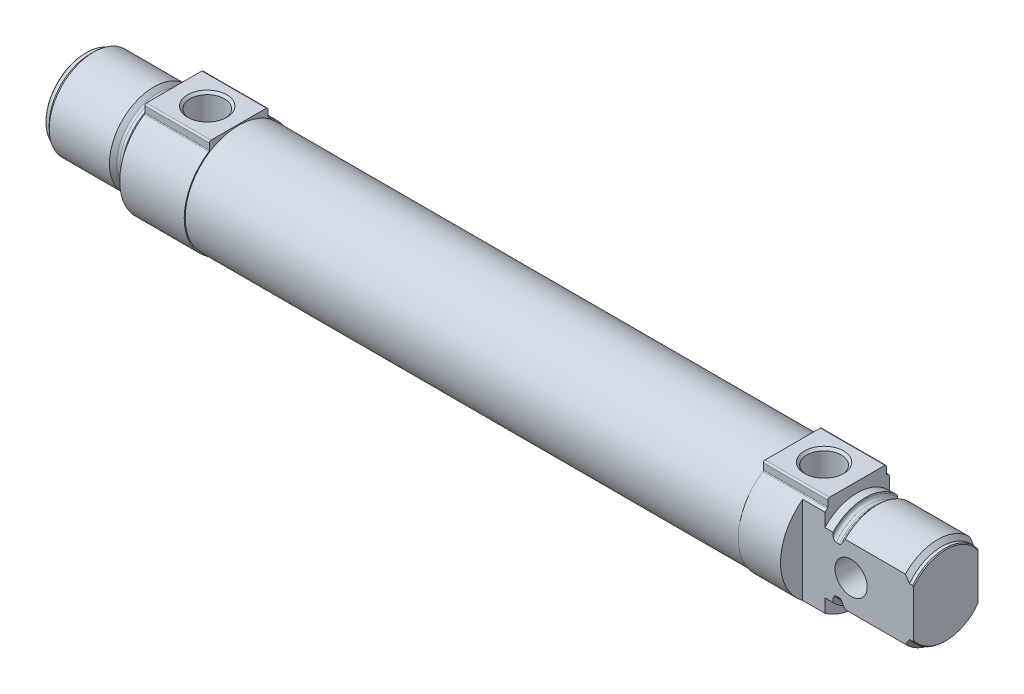
SolidWorks part; units mm, degrees
ref_plane "Ebene vorne" through (0, 0, 0) normal (0, 0, 1) x (1, 0, 0)
ref_plane "Ebene oben" through (0, 0, 0) normal (0, 1, 0) x (1, 0, 0)
ref_plane "Ebene rechts" through (0, 0, 0) normal (1, 0, 0) x (0, 0, -1)
sketch "Skizze1" plane through (0, 0, 0) normal (0, 0, 1) x (1, 0, 0)
  line L0 (0, 0) -> (0, 9.8)
  line L1 (0, 9.8) -> (0.2, 10)
  line L2 (0.2, 10) -> (1, 10)
  line L3 (1, 10) -> (2, 11)
  line L4 (2, 11) -> (16.95, 11)
  line L5 (16.95, 11) -> (17.8657, 10.0843)
  line L6 (18.4314, 9.85) -> (19.2, 9.85)
  line L7 (20, 10.65) -> (20, 11)
  line L8 (20, 11) -> (22, 11)
  line L9 (22, 11) -> (22, 0)
  line L10 (22, 0) -> (0, 0)
  line L11 (22, 0) -> (0, 0) construction
  arc A0 (17.8657, 10.0843) -> (18.4314, 9.85) centre (18.4314, 10.65) ccw
  arc A1 (19.2, 9.85) -> (20, 10.65) centre (19.2, 10.65) ccw
revolve "Rotation1" add sketch "Skizze1" angle 360 about L11 reverse direction yes
cosmetic thread "Gewindedarstellung1" parameters "D1"=15.87, "D2"=20.16
ref_plane "Ebene1" through (31.8, 0, 0) normal (1, 0, 0) x (0, 0, -1)
ref_plane "Ebene2" through (10.5, 0, 0) normal (1, 0, 0) x (0, 0, -1)
ref_plane "Ebene3" through (0, -16, 0) normal (0, 1, 0) x (1, 0, 0)
ref_plane "Ebene4" through (0, 14.9, 0) normal (0, 1, 0) x (1, 0, 0)
ref_plane "Ebene5" through (0, 0, 0) normal (0, 1, 0) x (1, 0, 0)
ref_plane "Ebene6" through (0, 0, 0) normal (0, 1, 0) x (1, 0, 0)
ref_plane "Ebene7" through (22, 0, 0) normal (1, 0, 0) x (0, 0, -1)
ref_plane "Ebene8" through (22, 0, 0) normal (1, 0, 0) x (0, 0, -1)
ref_plane "Ebene9" through (35, 0, 0) normal (1, 0, 0) x (0, 0, -1)
ref_plane "Ebene10" through (26.5, 0, 0) normal (1, 0, 0) x (0, 0, -1)
ref_plane "Ebene11" through (46.5, 0, 0) normal (1, 0, 0) x (0, 0, -1)
sketch "Skizze2" plane through (22, 0, 0) normal (1, 0, 0) x (0, 0, -1)
  line L0 (7.25, 11.5515) -> (7.25, 13.1)
  line L1 (6.85, 13.5) -> (-6.85, 13.5)
  line L2 (-7.25, 13.1) -> (-7.25, 11.5515)
  arc A0 (-7.3859, 11.3004) -> (7.3859, 11.3004) centre (0, 0) ccw
  arc A1 (7.3859, 11.3004) -> (7.25, 11.5515) centre (7.55, 11.5515) cw
  arc A2 (7.25, 13.1) -> (6.85, 13.5) centre (6.85, 13.1) ccw
  arc A3 (-6.85, 13.5) -> (-7.25, 13.1) centre (-6.85, 13.1) ccw
  arc A4 (-7.25, 11.5515) -> (-7.3859, 11.3004) centre (-7.55, 11.5515) cw
extrude "Aufsatz-Linear austragen1" add sketch "Skizze2" along normal blind 16
ref_plane "Ebene12" through (34, 0, 0) normal (1, 0, 0) x (0, 0, -1)
ref_plane "Ebene13" through (0, 0, 0) normal (0, 0, 1) x (1, 0, 0)
ref_plane "Ebene14" through (0, 0, -9.1) normal (0, 0, 1) x (1, 0, 0)
ref_plane "Ebene15" through (0, 0, 0) normal (0, 1, 0) x (1, 0, 0)
ref_plane "Ebene16" through (0, 6.9, 0) normal (0, 1, 0) x (1, 0, 0)
ref_plane "Ebene17" through (0, 0, -6.6) normal (0, 0, 1) x (1, 0, 0)
ref_plane "Ebene18" through (0, 0, 0) normal (0, 1, 0) x (1, 0, 0)
ref_plane "Ebene19" through (0, 6.9, 0) normal (0, 1, 0) x (1, 0, 0)
ref_plane "Ebene20" through (0, 7.8206, -1.379) normal (0, 0.9848, -0.1736) x (1, 0, 0)
ref_plane "Ebene21" through (0, 6.3434, -1.1185) normal (0, 0.9848, -0.1736) x (1, 0, 0)
sketch "Skizze3" plane through (0, 0, 0) normal (0, 0, 1) x (1, 0, 0)
  line L0 (38, 0) -> (38, 13.25)
  line L1 (38, 13.25) -> (175.5, 13.25)
  line L2 (175.5, 13.25) -> (175.5, 0)
  line L3 (175.5, 0) -> (38, 0)
  line L4 (175.5, 0) -> (38, 0) construction
revolve "Rotation2" add sketch "Skizze3" angle 360 about L4 reverse direction yes
ref_plane "Ebene22" through (175.5, 0, 0) normal (1, 0, 0) x (0, 0, -1)
sketch "Skizze4" plane through (175.5, 0, 0) normal (1, 0, 0) x (0, 0, -1)
  line L0 (7.25, 11.5515) -> (7.25, 13.1)
  line L1 (6.85, 13.5) -> (-6.85, 13.5)
  line L2 (-7.25, 13.1) -> (-7.25, 11.5515)
  arc A0 (-7.3859, 11.3004) -> (7.3859, 11.3004) centre (0, 0) ccw
  arc A1 (7.3859, 11.3004) -> (7.25, 11.5515) centre (7.55, 11.5515) cw
  arc A2 (7.25, 13.1) -> (6.85, 13.5) centre (6.85, 13.1) ccw
  arc A3 (-6.85, 13.5) -> (-7.25, 13.1) centre (-6.85, 13.1) ccw
  arc A4 (-7.25, 11.5515) -> (-7.3859, 11.3004) centre (-7.55, 11.5515) cw
extrude "Aufsatz-Linear austragen2" add sketch "Skizze4" along normal blind 16
ref_plane "Ebene23" through (179.3, 0, 0) normal (1, 0, 0) x (0, 0, -1)
ref_plane "Ebene24" through (179.5, 0, 0) normal (1, 0, 0) x (0, 0, -1)
ref_plane "Ebene25" through (0, 0, 6.6) normal (0, 0, 1) x (1, 0, 0)
ref_plane "Ebene26" through (0, 0, 0) normal (0, 1, 0) x (1, 0, 0)
ref_plane "Ebene27" through (0, 6.9, 0) normal (0, 1, 0) x (1, 0, 0)
ref_plane "Ebene28" through (0, 7.8206, 1.379) normal (0, 0.9848, 0.1736) x (1, 0, 0)
ref_plane "Ebene29" through (0, 6.3434, 1.1185) normal (0, 0.9848, 0.1736) x (1, 0, 0)
ref_plane "Ebene30" through (239.5, 0, 0) normal (1, 0, 0) x (0, 0, -1)
sketch "Skizze5" plane through (0, 0, 0) normal (0, 0, 1) x (1, 0, 0)
  line L0 (191.5, 0) -> (191.5, 11)
  line L1 (191.5, 11) -> (193.5, 11)
  line L2 (193.5, 11) -> (193.5, 10.65)
  line L3 (194.3, 9.85) -> (195.0686, 9.85)
  line L4 (195.6343, 10.0843) -> (196.55, 11)
  line L5 (196.55, 11) -> (211.5, 11)
  line L6 (211.5, 11) -> (212.5, 10)
  line L7 (212.5, 10) -> (213.3, 10)
  line L8 (213.3, 10) -> (213.5, 9.8)
  line L9 (213.5, 9.8) -> (213.5, 0)
  line L10 (213.5, 0) -> (191.5, 0)
  line L11 (213.5, 0) -> (191.5, 0) construction
  arc A0 (193.5, 10.65) -> (194.3, 9.85) centre (194.3, 10.65) ccw
  arc A1 (195.0686, 9.85) -> (195.6343, 10.0843) centre (195.0686, 10.65) ccw
revolve "Rotation3" add sketch "Skizze5" angle 360 about L11 reverse direction yes
cosmetic thread "Gewindedarstellung2" parameters "D1"=14.87, "D2"=20.16
ref_plane "Ebene31" through (226.5, 0, 0) normal (1, 0, 0) x (0, 0, -1)
ref_plane "Ebene32" through (235, 0, 0) normal (1, 0, 0) x (0, 0, -1)
ref_plane "Ebene33" through (215, 0, 0) normal (1, 0, 0) x (0, 0, -1)
sketch "Skizze6" plane through (0, 0, 0) normal (0, 1, 0) x (1, 0, 0)
  line L0 (186, 24) -> (186, 8)
  line L1 (186, 8) -> (213.5, 8)
  line L2 (213.5, 8) -> (213.5, -8)
  line L3 (213.5, -8) -> (186, -8)
  line L4 (186, -8) -> (186, -24)
  line L5 (186, -24) -> (229.5, -24)
  line L6 (229.5, -24) -> (229.5, 24)
  line L7 (229.5, 24) -> (186, 24)
extrude "Schnitt-Linear austragen1" cut sketch "Skizze6" along normal blind 13.5 and the other way blind 13.5
ref_plane "Ebene34" through (198, 0, 0) normal (1, 0, 0) x (0, 0, -1)
hole_wizard "Bohrung1" positions "Skizze8" profile "Skizze7" legacy
sketch "Skizze8" plane through (0, 0, -8) normal (0, 0, -1) x (-1, 0, 0)
  point P0 (-198, 0)
sketch "Skizze7" plane through (198, 0, -8) normal (1, 0, 0) x (0, 1, 0)
  line L0 (0, 0) -> (0, 16)
  line L1 (0, 16) -> (4, 16)
  line L2 (4, 16) -> (4, 0)
  line L3 (4, 0) -> (0, 0)
  line L4 (0, 110) -> (0, -10) construction
  dimension "Durchmesser" = 8
  dimension "Tiefe" = 16
hole_wizard "Bohrung2" positions "Skizze10" profile "Skizze9" legacy
sketch "Skizze10" plane through (0, 13.5, 0) normal (0, 1, 0) x (1, 0, 0)
  point P0 (30.2, 0)
sketch "Skizze9" plane through (30.2, 13.5, 0) normal (1, 0, 0) x (0, 0, 1)
  line L0 (0, 0) -> (0, 13.5)
  line L1 (0, 13.5) -> (4.283, 13.5)
  line L2 (4.283, 13.5) -> (4.283, 0.581)
  line L3 (4.283, 0.581) -> (4.864, 0)
  line L4 (4.864, 0) -> (0, 0)
  line L5 (0, -6.4453) -> (0, 115.525) construction
  line L6 (-4.283, 0.581) -> (-4.864, 0) construction
  dimension "Durchmesser" = 8.566
  dimension "Tiefe" = 13.5
  dimension "Senkwinkel1" = 90
  dimension "Senkdurchmesser3" = 9.728
cosmetic thread "Gewindedarstellung3" parameters "D1"=8.5, "D2"=9.728
hole_wizard "Bohrung3" positions "Skizze12" profile "Skizze11" legacy
sketch "Skizze12" plane through (0, 13.5, 0) normal (0, 1, 0) x (1, 0, 0)
  point P0 (183.3, 0)
sketch "Skizze11" plane through (183.3, 13.5, 0) normal (1, 0, 0) x (0, 0, 1)
  line L0 (0, 0) -> (0, 18.4728)
  line L1 (0, 18.4728) -> (4.283, 16)
  line L2 (4.283, 16) -> (4.283, 0.581)
  line L3 (4.283, 0.581) -> (4.864, 0)
  line L4 (4.864, 0) -> (0, 0)
  line L5 (0, -14.3089) -> (0, 102.4216) construction
  line L6 (0, 18.4728) -> (-4.283, 16) construction
  line L7 (-4.283, 0.581) -> (-4.864, 0) construction
  dimension "Durchmesser" = 8.566
  dimension "Tiefe" = 16
  dimension "Senkdurchmesser1" = 9.728
  dimension "Senkwinkel1" = 90
  dimension "Spitzenwinkel" = 120
cosmetic thread "Gewindedarstellung4" parameters "D1"=8, "D2"=9.728
sketch "Skizze13" plane through (0, 0, 0) normal (0, 0, 1) x (1, 0, 0)
  line L0 (-6, 0) -> (-6, 5)
  line L1 (-6, 5) -> (52.6, 5)
  line L2 (52.6, 5) -> (52.6, 12.5)
  line L3 (52.6, 12.5) -> (158.85, 12.5)
  line L4 (158.85, 12.5) -> (158.85, 0)
  line L5 (158.85, 0) -> (-6, 0)
  line L6 (158.85, 0) -> (-6, 0) construction
revolve "Schnitt-Rotation1" cut sketch "Skizze13" angle 360 about L6 reverse direction yes
ref_plane "Ebene35" through (-6, 0, 0) normal (1, 0, 0) x (0, 0, -1)
ref_plane "Ebene36" through (0, 13.5, 0) normal (0, 1, 0) x (1, 0, 0)
ref_plane "Ebene37" through (8.5, 0, 0) normal (1, 0, 0) x (0, 0, -1)
ref_plane "Ebene38" through (0, 0, 0) normal (1, 0, 0) x (0, 0, -1)
ref_plane "Ebene39" through (22, 0, 0) normal (1, 0, 0) x (0, 0, -1)
ref_plane "Ebene40" through (191.5, 0, 0) normal (1, 0, 0) x (0, 0, -1)
ref_plane "Ebene41" through (22, 0, 0) normal (1, 0, 0) x (0, 0, -1)
ref_plane "Ebene42" through (0, 13.5, 0) normal (0, 1, 0) x (1, 0, 0)
ref_plane "Ebene43" through (47.5, 0, 0) normal (1, 0, 0) x (0, 0, -1)
ref_plane "Ebene44" through (166, 0, 0) normal (1, 0, 0) x (0, 0, -1)
ref_plane "Ebene45" through (0, 0, 0) normal (0, 0, 1) x (1, 0, 0)
ref_plane "Ebene46" through (22, 0, 0) normal (1, 0, 0) x (0, 0, -1)
ref_plane "Ebene47" through (0, 13.5, 0) normal (0, 1, 0) x (1, 0, 0)
ref_plane "FDT_FRONT XY" through (22, 0, 0) normal (1, 0, 0) x (0, 0, -1)
ref_plane "FDT_FRONT XZ" through (0, 0, 0) normal (0, -1, 0) x (-1, 0, 0)
ref_plane "FDT_FRONT YZ" through (0, 0, 0) normal (0, 0, -1) x (-1, 0, 0)
ref_axis "FDT_FRONT X" through (22, 0, 80.9) along (0, 0, -1)
ref_axis "FDT_FRONT Y" through (22, -50, 0) along (0, 1, 0)
ref_axis "FDT_FRONT Z" through (80.9, 0, 0) along (-1, 0, 0)
sketch3d "FDT_FRONT"
  point P0 (22, 0, 0)
ref_plane "FDT_QSFRONT XY" through (0, 13.5, 0) normal (0, 1, 0) x (1, 0, 0)
ref_plane "FDT_QSFRONT XZ" through (30.2, 0, 0) normal (-1, 0, 0) x (0, 0, 1)
ref_plane "FDT_QSFRONT YZ" through (0, 0, 0) normal (0, 0, 1) x (1, 0, 0)
ref_axis "FDT_QSFRONT X" through (30.2, 13.5, -50) along (0, 0, 1)
ref_axis "FDT_QSFRONT Y" through (-80.9, 13.5, 0) along (1, 0, 0)
ref_axis "FDT_QSFRONT Z" through (30.2, 50, 0) along (0, -1, 0)
sketch3d "FDT_QSFRONT"
  point P0 (30.2, 13.5, 0)
ref_plane "FDT_QSREAR XY" through (0, 13.5, 0) normal (0, 1, 0) x (1, 0, 0)
ref_plane "FDT_QSREAR XZ" through (183.3, 0, 0) normal (-1, 0, 0) x (0, 0, 1)
ref_plane "FDT_QSREAR YZ" through (0, 0, 0) normal (0, 0, 1) x (1, 0, 0)
ref_axis "FDT_QSREAR X" through (183.3, 13.5, -50) along (0, 0, 1)
ref_axis "FDT_QSREAR Y" through (-80.9, 13.5, 0) along (1, 0, 0)
ref_axis "FDT_QSREAR Z" through (183.3, 50, 0) along (0, -1, 0)
sketch3d "FDT_QSREAR"
  point P0 (183.3, 13.5, 0)
ref_plane "FDT_REAR XY" through (191.5, 0, 0) normal (-1, 0, 0) x (0, 0, 1)
ref_plane "FDT_REAR XZ" through (0, 0, 0) normal (0, 1, 0) x (1, 0, 0)
ref_plane "FDT_REAR YZ" through (0, 0, 0) normal (0, 0, -1) x (-1, 0, 0)
ref_axis "FDT_REAR X" through (191.5, 0, 80.9) along (0, 0, -1)
ref_axis "FDT_REAR Y" through (191.5, 50, 0) along (0, -1, 0)
ref_axis "FDT_REAR Z" through (-80.9, 0, 0) along (1, 0, 0)
sketch3d "FDT_REAR"
  point P0 (191.5, 0, 0)
ref_plane "FDT_SMBR1 XY" through (47.5, 0, 0) normal (-1, 0, 0) x (0, 0, 1)
ref_plane "FDT_SMBR1 XZ" through (0, 0, 0) normal (0, -1, 0) x (-1, 0, 0)
ref_plane "FDT_SMBR1 YZ" through (0, 0, 0) normal (0, 0, 1) x (1, 0, 0)
ref_axis "FDT_SMBR1 X" through (47.5, 0, -80.9) along (0, 0, 1)
ref_axis "FDT_SMBR1 Y" through (47.5, -50, 0) along (0, 1, 0)
ref_axis "FDT_SMBR1 Z" through (-80.9, 0, 0) along (1, 0, 0)
sketch3d "FDT_SMBR1"
  point P0 (47.5, 0, 0)
ref_plane "FDT_SMBR2 XY" through (166, 0, 0) normal (-1, 0, 0) x (0, 0, 1)
ref_plane "FDT_SMBR2 XZ" through (0, 0, 0) normal (0, -1, 0) x (-1, 0, 0)
ref_plane "FDT_SMBR2 YZ" through (0, 0, 0) normal (0, 0, 1) x (1, 0, 0)
ref_axis "FDT_SMBR2 X" through (166, 0, -80.9) along (0, 0, 1)
ref_axis "FDT_SMBR2 Y" through (166, -50, 0) along (0, 1, 0)
ref_axis "FDT_SMBR2 Z" through (-80.9, 0, 0) along (1, 0, 0)
sketch3d "FDT_SMBR2"
  point P0 (166, 0, 0)
ref_plane "FDT_SWIVELAXIS XY" through (0, 0, 0) normal (0, 0, 1) x (1, 0, 0)
ref_plane "FDT_SWIVELAXIS XZ" through (0, 0, 0) normal (0, -1, 0) x (-1, 0, 0)
ref_plane "FDT_SWIVELAXIS YZ" through (198, 0, 0) normal (1, 0, 0) x (0, 0, -1)
ref_axis "FDT_SWIVELAXIS X" through (-80.9, 0, 0) along (1, 0, 0)
ref_axis "FDT_SWIVELAXIS Y" through (198, -50, 0) along (0, 1, 0)
ref_axis "FDT_SWIVELAXIS Z" through (198, 0, 80.9) along (0, 0, -1)
sketch3d "FDT_SWIVELAXIS"
  point P0 (198, 0, 0)
ref_plane "NUT XY" through (8.5, 0, 0) normal (1, 0, 0) x (0, 0, -1)
ref_plane "NUT XZ" through (0, 0, 0) normal (0, -1, 0) x (-1, 0, 0)
ref_plane "NUT YZ" through (0, 0, 0) normal (0, 0, -1) x (-1, 0, 0)
ref_axis "NUT X" through (8.5, 0, 80.9) along (0, 0, -1)
ref_axis "NUT Y" through (8.5, -50, 0) along (0, 1, 0)
ref_axis "NUT Z" through (80.9, 0, 0) along (-1, 0, 0)
sketch3d "NUT"
  point P0 (8.5, 0, 0)
ref_plane "ZR XY" through (0, 0, 0) normal (1, 0, 0) x (0, 0, -1)
ref_plane "ZR XZ" through (0, 0, 0) normal (0, -1, 0) x (-1, 0, 0)
ref_plane "ZR YZ" through (0, 0, 0) normal (0, 0, -1) x (-1, 0, 0)
ref_axis "ZR X" through (0, 0, 80.9) along (0, 0, -1)
ref_axis "ZR Y" through (0, -50, 0) along (0, 1, 0)
ref_axis "ZR Z" through (80.9, 0, 0) along (-1, 0, 0)
sketch3d "ZR"
  point P0 (0, 0, 0)
ref_plane "ZYL XY" through (22, 0, 0) normal (1, 0, 0) x (0, 0, -1)
ref_plane "ZYL XZ" through (0, 0, 0) normal (0, -1, 0) x (-1, 0, 0)
ref_plane "ZYL YZ" through (0, 0, 0) normal (0, 0, -1) x (-1, 0, 0)
ref_axis "ZYL X" through (22, 0, 80.9) along (0, 0, -1)
ref_axis "ZYL Y" through (22, -50, 0) along (0, 1, 0)
ref_axis "ZYL Z" through (80.9, 0, 0) along (-1, 0, 0)
sketch3d "ZYL"
  point P0 (22, 0, 0)
